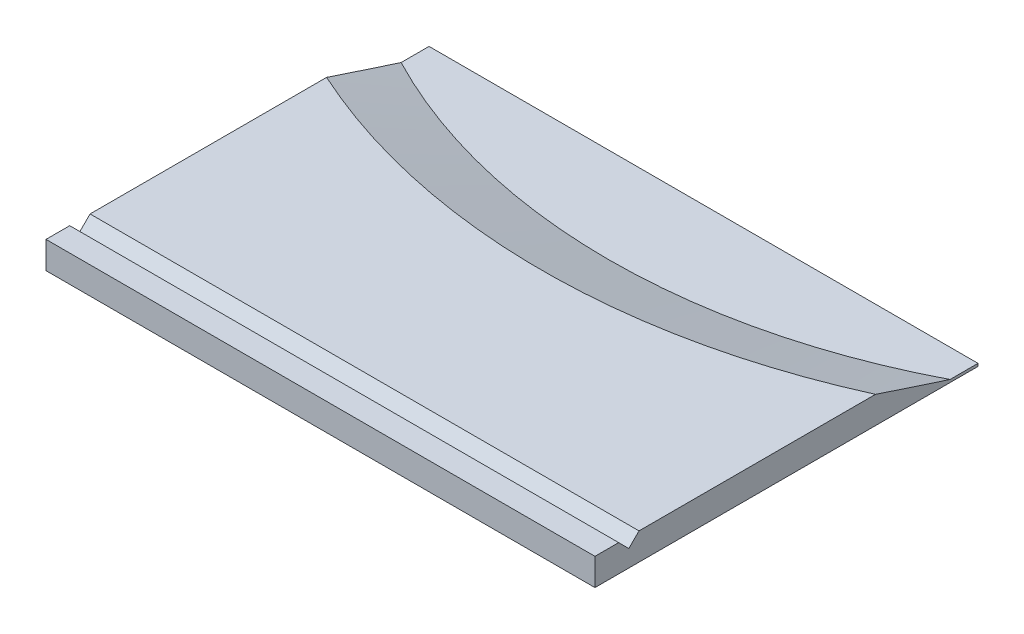
SolidWorks part; units mm, degrees
ref_plane "Front" through (0, 0, 0) normal (0, 0, 1) x (1, 0, 0)
ref_plane "Top" through (0, 0, 0) normal (0, 1, 0) x (1, 0, 0)
ref_plane "Side" through (0, 0, 0) normal (1, 0, 0) x (0, 0, -1)
ref_axis "X_Axis" through (-20.1896, 0, 0) along (1, 0, 0)
ref_axis "Y_Axis" through (0, -14.8261, 0) along (0, 1, 0)
ref_axis "Z_Axis" through (0, 0, -19.842) along (0, 0, 1)
sketch "Sketch1" plane through (0, 0, 0) normal (0, 1, 0) x (1, 0, 0)
  line L1 (20.25, 14.13) -> (-20.25, 14.13)
  line L2 (20.25, 14.13) -> (20.25, -14.13)
  line L3 (20.25, -14.13) -> (-20.25, -14.13)
  line L4 (-20.25, 14.13) -> (-20.25, -14.13)
  line L5 (20.25, 14.13) -> (-20.25, -14.13) construction
  line L6 (20.25, -14.13) -> (-20.25, 14.13) construction
  point P0 (0, 0)
  dimension "D1" = 40.5
  dimension "D2" = 28.26
extrude "Boss-Extrude1" add sketch "Sketch1" along normal blind 2
sketch "Sketch2" plane through (0, 2, 0) normal (0, 1, 0) x (1, 0, 0)
  line L0 (0, 7.13) -> (34.095, 7.13) construction
  line L1 (20.25, 14.13) -> (-20.25, 14.13) construction
  circle A0 centre (0, 51.13) radius 44
  dimension "D1" = 88
  dimension "D2" = 7
extrude "Cut-Extrude1" cut sketch "Sketch2" against normal blind 1.8
chamfer "Chamfer1" distance 1.8 angle 70 1 edges at (0, 2, -7.13) first distance on face at (0, 1.1, -9.5984)
sketch "Sketch3" plane through (20.25, 0, 0) normal (1, 0, 0) x (0, 0, -1)
  line L0 (-12.38, 2) -> (-11.63, 1.25)
  line L1 (-14.13, 2) -> (6.57, 2) construction
  line L2 (-11.63, 1.25) -> (-10.88, 2)
  line L3 (-10.88, 2) -> (-10.88, 3.4845)
  line L4 (-10.88, 3.4845) -> (-12.38, 3.4845)
  line L5 (-12.38, 3.4845) -> (-12.38, 2)
  line L6 (-11.63, 0) -> (-11.63, 3.4845) construction
  line L7 (-14.13, 0) -> (14.13, 0) construction
  line L8 (-14.13, 2) -> (-14.13, 0) construction
  point P13 (-11.63, 1.3198)
  dimension "D1" = 2.5
  dimension "D2" = 1.5
extrude "Cut-Extrude2" cut sketch "Sketch3" against normal through all
